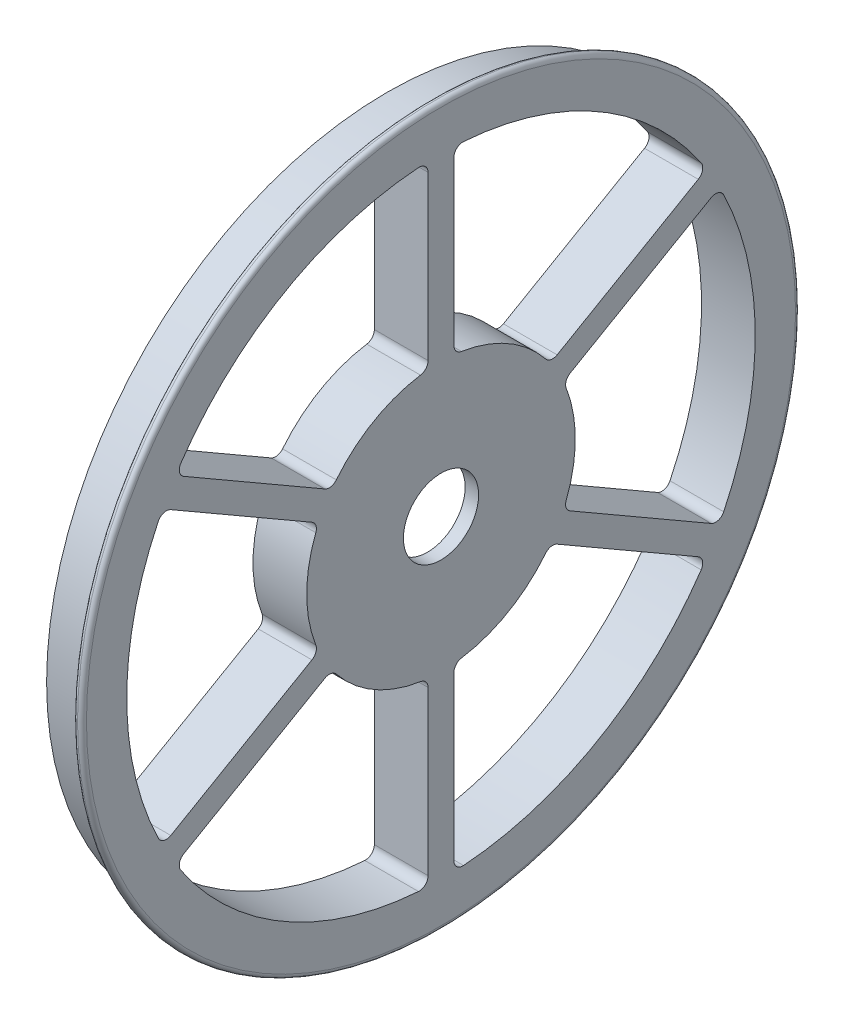
SolidWorks part; units mm, degrees
ref_plane "Front Plane" through (0, 0, 0) normal (0, 0, 1) x (1, 0, 0)
ref_plane "Top Plane" through (0, 0, 0) normal (0, 1, 0) x (1, 0, 0)
ref_plane "Right Plane" through (0, 0, 0) normal (1, 0, 0) x (0, 0, -1)
sketch "Sketch1" plane through (0, 0, 0) normal (0, 0, 1) x (1, 0, 0)
  line L2 (-3, 0) -> (-3, 38.05)
  line L5 (-3, 38.05) -> (2, 38.05)
  line L14 (2, 38.05) -> (2, 40.1)
  line L15 (2, 40.1) -> (3, 40.1)
  line L16 (3, 40.1) -> (3, 0)
  line L17 (3, 0) -> (-3, 0)
  point P0 (0, 0)
  dimension "D3" = 40.1
  dimension "D1" = 1
  dimension "D2" = 5
  dimension "D4" = 38.05
revolve "Revolve2" add sketch "Sketch1" angle 360 about L17
sketch "Sketch2" plane through (3, 0, 0) normal (-1, 0, 0) x (0, 0, 1)
  line L0 (0, 0) -> (13.6518, 0) construction
  line L1 (14.4156, 6.6562) -> (30.1772, 15.7562)
  line L2 (13.6518, 6.2152) -> (13.6518, -6.2152) construction
  line L3 (14.4156, -6.6562) -> (30.1772, -15.7562)
  line L4 (31.0935, 16.2852) -> (31.0935, -16.2852) construction
  line L5 (2.8868, 0) -> (13.6518, 6.2152) construction
  line L6 (2.8868, 0) -> (1.4434, 2.5) construction
  line L7 (1.4434, 2.5) -> (-1.4434, 2.5) construction
  line L8 (-1.4434, 2.5) -> (-2.8868, 0) construction
  line L9 (-2.8868, 0) -> (-1.4434, -2.5) construction
  line L10 (-1.4434, -2.5) -> (1.4434, -2.5) construction
  line L11 (1.4434, -2.5) -> (2.8868, 0) construction
  line L12 (13.6518, 0) -> (31.0935, 0) construction
  line L13 (13.6518, -6.2152) -> (2.8868, 0) construction
  line L14 (12.9722, -9.1562) -> (28.7339, -18.2562)
  line L15 (1.4434, -15.8123) -> (1.4434, -34.0123)
  line L16 (-1.4434, -15.8123) -> (-1.4434, -34.0123)
  line L17 (-12.9722, -9.1562) -> (-28.7339, -18.2562)
  line L18 (-14.4156, -6.6562) -> (-30.1772, -15.7562)
  line L19 (-14.4156, 6.6562) -> (-30.1772, 15.7562)
  line L20 (-12.9722, 9.1562) -> (-28.7339, 18.2562)
  line L21 (-1.4434, 15.8123) -> (-1.4434, 34.0123)
  line L22 (1.4434, 15.8123) -> (1.4434, 34.0123)
  line L23 (12.9722, 9.1562) -> (28.7339, 18.2562)
  arc A0 (31.5769, 15.3268) -> (31.5769, -15.3268) centre (0, 0) cw
  circle A2 centre (0, 0) radius 2.5 construction
  arc A3 (13.9833, 5.4283) -> (13.9833, -5.4283) centre (0, 0) cw
  arc A4 (13.9833, -5.4283) -> (14.4156, -6.6562) centre (14.9156, -5.7901) ccw
  arc A5 (14.4156, 6.6562) -> (13.9833, 5.4283) centre (14.9156, 5.7901) ccw
  arc A6 (30.1772, -15.7562) -> (31.5769, -15.3268) centre (30.6772, -14.8901) ccw
  arc A7 (31.5769, 15.3268) -> (30.1772, 15.7562) centre (30.6772, 14.8901) ccw
  arc A8 (29.0618, -19.683) -> (28.7339, -18.2562) centre (28.2339, -19.1222) ccw
  arc A9 (29.0618, -19.683) -> (2.515, -35.0098) centre (0, 0) cw
  arc A10 (1.4434, -34.0123) -> (2.515, -35.0098) centre (2.4434, -34.0123) ccw
  arc A11 (2.2907, -14.8241) -> (1.4434, -15.8123) centre (2.4434, -15.8123) ccw
  arc A12 (11.6927, -9.3958) -> (2.2907, -14.8241) centre (0, 0) cw
  arc A13 (12.9722, -9.1562) -> (11.6927, -9.3958) centre (12.4722, -10.0222) ccw
  arc A14 (-2.515, -35.0098) -> (-1.4434, -34.0123) centre (-2.4434, -34.0123) ccw
  arc A15 (-2.515, -35.0098) -> (-29.0618, -19.683) centre (0, 0) cw
  arc A16 (-28.7339, -18.2562) -> (-29.0618, -19.683) centre (-28.2339, -19.1222) ccw
  arc A17 (-11.6927, -9.3958) -> (-12.9722, -9.1562) centre (-12.4722, -10.0222) ccw
  arc A18 (-2.2907, -14.8241) -> (-11.6927, -9.3958) centre (0, 0) cw
  arc A19 (-1.4434, -15.8123) -> (-2.2907, -14.8241) centre (-2.4434, -15.8123) ccw
  arc A20 (-31.5769, -15.3268) -> (-30.1772, -15.7562) centre (-30.6772, -14.8901) ccw
  arc A21 (-31.5769, -15.3268) -> (-31.5769, 15.3268) centre (0, 0) cw
  arc A22 (-30.1772, 15.7562) -> (-31.5769, 15.3268) centre (-30.6772, 14.8901) ccw
  arc A23 (-13.9833, 5.4283) -> (-14.4156, 6.6562) centre (-14.9156, 5.7901) ccw
  arc A24 (-13.9833, -5.4283) -> (-13.9833, 5.4283) centre (0, 0) cw
  arc A25 (-14.4156, -6.6562) -> (-13.9833, -5.4283) centre (-14.9156, -5.7901) ccw
  arc A26 (-29.0618, 19.683) -> (-28.7339, 18.2562) centre (-28.2339, 19.1222) ccw
  arc A27 (-29.0618, 19.683) -> (-2.515, 35.0098) centre (0, 0) cw
  arc A28 (-1.4434, 34.0123) -> (-2.515, 35.0098) centre (-2.4434, 34.0123) ccw
  arc A29 (-2.2907, 14.8241) -> (-1.4434, 15.8123) centre (-2.4434, 15.8123) ccw
  arc A30 (-11.6927, 9.3958) -> (-2.2907, 14.8241) centre (0, 0) cw
  arc A31 (-12.9722, 9.1562) -> (-11.6927, 9.3958) centre (-12.4722, 10.0222) ccw
  arc A32 (2.515, 35.0098) -> (1.4434, 34.0123) centre (2.4434, 34.0123) ccw
  arc A33 (2.515, 35.0098) -> (29.0618, 19.683) centre (0, 0) cw
  arc A34 (28.7339, 18.2562) -> (29.0618, 19.683) centre (28.2339, 19.1222) ccw
  arc A35 (11.6927, 9.3958) -> (12.9722, 9.1562) centre (12.4722, 10.0222) ccw
  arc A36 (2.2907, 14.8241) -> (11.6927, 9.3958) centre (0, 0) cw
  arc A37 (1.4434, 15.8123) -> (2.2907, 14.8241) centre (2.4434, 15.8123) ccw
  circle A39 centre (0, 0) radius 40.1 construction
  point P92 (0, 0)
  dimension "D5" = 5
  dimension "D2" = 15
  dimension "D3" = 1
  dimension "D1" = 30
  dimension "D4" = 5
  dimension "D6" = 6
extrude "Cut-Extrude2" cut sketch "Sketch2" along normal through all
fillet "Fillet1" radius 0.5 3 edges at (3, 0, -40.1) (2, 0, -40.1) (2, 0, -38.05)
sketch "Sketch7" plane through (3, 0, 0) normal (1, 0, 0) x (0, 0, -1)
  circle A0 centre (0, 0) radius 4.2
  dimension "D1" = 8.4
extrude "Cut-Extrude5" cut sketch "Sketch7" against normal through all both and the other way through all
sketch "Sketch8" plane through (-3, 0, 0) normal (1, 0, 0) x (0, 0, -1)
  circle A0 centre (0, 0) radius 11.25
  dimension "D1" = 22.5
extrude "Cut-Extrude6" cut sketch "Sketch8" along normal blind 4.5
equation "\"SpokeWidth\"= 5"
equation "\"D5@Sketch2\" = \"SpokeWidth\""
equation "\"HubDiameter\"= 30"
equation "\"D2@Sketch2\"=\"HubDiameter\"/2"
equation "\"PulleyDiameter\"= 3in"
equation "\"PulleyWidth\"= 3.45in"
equation "\"RimWidth\"= 5"
equation "\"D4@Sketch2\"=\"RimWidth\""
